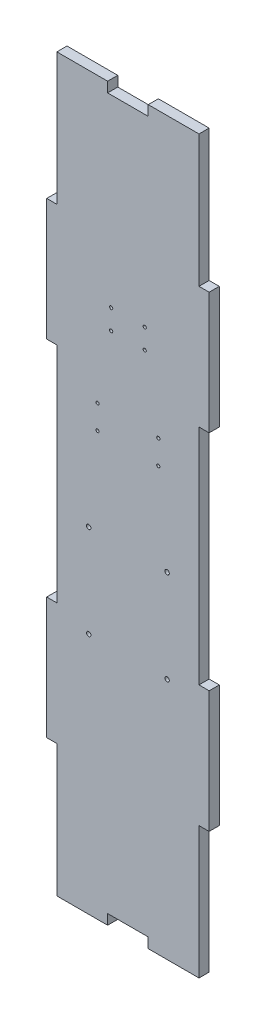
SolidWorks part; units mm, degrees
ref_plane "Front Plane" through (0, 0, 0) normal (0, 0, 1) x (1, 0, 0)
ref_plane "Top Plane" through (0, 0, 0) normal (0, 1, 0) x (1, 0, 0)
ref_plane "Right Plane" through (0, 0, 0) normal (1, 0, 0) x (0, 0, -1)
sketch "Sketch1" plane through (0, 0, 0) normal (0, 0, 1) x (1, 0, 0)
  line L1 (-192.6077, 179.9617) -> (-103.7077, 179.9617)
  line L2 (-192.6077, 179.9617) -> (-192.6077, -277.2383)
  line L3 (-192.6077, -277.2383) -> (-103.7077, -277.2383)
  line L4 (-103.7077, 179.9617) -> (-103.7077, -277.2383)
  dimension "D1" = 457.2
  dimension "D2" = 88.9
extrude "Boss-Extrude1" add sketch "Sketch1" along normal blind 6.35
sketch "Sketch2" plane through (0, 0, 6.35) normal (0, 0, 1) x (1, 0, 0)
  line L0 (-192.6077, 179.9617) -> (-192.6077, -277.2383) construction
  line L1 (-198.9577, 97.4117) -> (-192.6077, 97.4117)
  line L2 (-198.9577, 97.4117) -> (-198.9577, 21.2117)
  line L3 (-198.9577, 21.2117) -> (-192.6077, 21.2117)
  line L4 (-192.6077, 97.4117) -> (-192.6077, 21.2117)
  line L6 (-198.9577, -118.4883) -> (-192.6077, -118.4883)
  line L7 (-198.9577, -118.4883) -> (-198.9577, -194.6883)
  line L8 (-198.9577, -194.6883) -> (-192.6077, -194.6883)
  line L9 (-192.6077, -118.4883) -> (-192.6077, -194.6883)
  line L10 (-148.1577, 179.9617) -> (-148.1577, -277.2383) construction
  line L11 (-103.7077, 179.9617) -> (-192.6077, 179.9617) construction
  line L12 (-192.6077, -277.2383) -> (-103.7077, -277.2383) construction
  line L13 (-97.3577, -194.6883) -> (-103.7077, -194.6883)
  line L14 (-97.3577, -118.4883) -> (-97.3577, -194.6883)
  line L15 (-103.7077, -118.4883) -> (-103.7077, -194.6883)
  line L16 (-97.3577, -118.4883) -> (-103.7077, -118.4883)
  line L17 (-97.3577, 21.2117) -> (-103.7077, 21.2117)
  line L18 (-97.3577, 97.4117) -> (-97.3577, 21.2117)
  line L19 (-103.7077, 97.4117) -> (-103.7077, 21.2117)
  line L20 (-97.3577, 97.4117) -> (-103.7077, 97.4117)
  dimension "D1" = 82.55
  dimension "D4" = 82.55
  dimension "D5" = 6.35
extrude "Boss-Extrude4" add sketch "Sketch2" against normal through all
sketch "Sketch3" plane through (0, 0, 6.35) normal (0, 0, 1) x (1, 0, 0)
  line L0 (-192.6077, -277.2383) -> (-103.7077, -277.2383) construction
  line L1 (-160.8577, -277.2383) -> (-135.4577, -277.2383)
  line L2 (-160.8577, -277.2383) -> (-160.8577, -270.8883)
  line L3 (-160.8577, -270.8883) -> (-135.4577, -270.8883)
  line L4 (-135.4577, -277.2383) -> (-135.4577, -270.8883)
  line L5 (-148.1577, 179.9617) -> (-148.1577, -277.2383) construction
  line L6 (-103.7077, 179.9617) -> (-192.6077, 179.9617) construction
  line L7 (-192.6077, -194.6883) -> (-192.6077, -277.2383) construction
  line L11 (-103.7077, 97.4117) -> (-103.7077, 179.9617) construction
  line L12 (-160.8577, 179.9617) -> (-135.4577, 179.9617)
  line L13 (-160.8577, 179.9617) -> (-160.8577, 173.6117)
  line L14 (-160.8577, 173.6117) -> (-135.4577, 173.6117)
  line L15 (-135.4577, 179.9617) -> (-135.4577, 173.6117)
  dimension "D5" = 6.35
  dimension "D2" = 25.4
  dimension "D3" = 6.35
  dimension "D4" = 25.4
  dimension "D6" = 31.75
  dimension "D1" = 31.75
extrude "Cut-Extrude1" cut sketch "Sketch3" against normal blind 6.35
sketch "Sketch4" plane through (0, 0, 0) normal (0, 0, 1) x (1, 0, 0)
  line L0 (-192.6077, -277.2383) -> (-160.8577, -277.2383) construction
  line L1 (-175.6577, -65.2383) -> (-120.6577, -65.2383) construction
  line L2 (-175.6577, -65.2383) -> (-175.6577, -150.2383) construction
  line L3 (-175.6577, -150.2383) -> (-120.6577, -150.2383) construction
  line L4 (-120.6577, -65.2383) -> (-120.6577, -150.2383) construction
  line L5 (-148.1577, -65.2383) -> (-148.1577, -150.2383) construction
  line L6 (-175.6577, -107.7383) -> (-120.6577, -107.7383) construction
  line L7 (-103.7077, -118.4883) -> (-103.7077, 21.2117) construction
  line L8 (-160.6355, 60.3617) -> (-135.6355, 60.3617) construction
  line L9 (-160.6355, 60.3617) -> (-160.6355, 36.3617) construction
  line L10 (-160.6355, 36.3617) -> (-135.6355, 36.3617) construction
  line L11 (-135.6355, 60.3617) -> (-135.6355, 36.3617) construction
  line L12 (-148.1577, 173.6117) -> (-148.1577, -270.8883) construction
  line L13 (-160.8577, 173.6117) -> (-135.4577, 173.6117) construction
  line L14 (-135.4577, -270.8883) -> (-160.8577, -270.8883) construction
  line L15 (-148.1577, 4.9389) -> (-148.1577, -15.0611) construction
  line L16 (-169.6577, 4.9389) -> (-126.6577, 4.9389) construction
  line L17 (-169.6577, 4.9389) -> (-169.6577, -15.0611) construction
  line L18 (-169.6577, -15.0611) -> (-126.6577, -15.0611) construction
  line L19 (-126.6577, 4.9389) -> (-126.6577, -15.0611) construction
  line L20 (-169.6577, -5.0611) -> (-126.6577, -5.0611) construction
  circle A0 centre (-172.6577, -67.3936) radius 1.375
  circle A1 centre (-123.6577, -67.3936) radius 1.375
  circle A2 centre (-123.6576, -125.3936) radius 1.375
  circle A3 centre (-172.6577, -125.3936) radius 1.375
  circle A4 centre (-158.6355, 58.3617) radius 1
  circle A5 centre (-158.6355, 45.8617) radius 1
  circle A6 centre (-137.6355, 58.3617) radius 1
  circle A7 centre (-137.6355, 45.8617) radius 1
  circle A8 centre (-167.1577, 2.4389) radius 1
  circle A9 centre (-129.1577, 2.4389) radius 1
  circle A10 centre (-129.1577, -12.5611) radius 1
  circle A11 centre (-167.1577, -12.5611) radius 1
  dimension "D5" = 2.75
  dimension "D4" = 2.75
  dimension "D9" = 2
  dimension "D23" = 2
  dimension "D1" = 127
  dimension "D2" = 85
  dimension "D3" = 55
  dimension "D6" = 58
  dimension "D7" = 25
  dimension "D8" = 24
  dimension "D10" = 21
  dimension "D11" = 12.5
  dimension "D12" = 9.5
  dimension "D13" = 2
  dimension "D14" = 2
  dimension "D15" = 2
  dimension "D16" = 31.9278
  dimension "D17" = 101.6
  dimension "D18" = 0
  dimension "D19" = 49
  dimension "D20" = 20
  dimension "D21" = 43
  dimension "D22" = 0
  dimension "D24" = 2.5
  dimension "D25" = 2.5
extrude "Cut-Extrude5" cut sketch "Sketch4" against normal through all and the other way through all
equation "\"width\"= 3.5in"
equation "\"Height\"= 18in"
equation "\"thick\"= 0.25"
equation "\"D1@Sketch1\"=\"Height\""
equation "\"D2@Sketch1\"=\"width\""
equation "\"D1@Boss-Extrude1\"=\"thick\""
equation "\"D5@Sketch2\"=\"thick\""
equation "\"D1\"= \"thick\""
equation "\"D3@Sketch3\"=\"thick\""
equation "\"D1@Cut-Extrude1\"=\"thick\""
equation "\"D5@Sketch3\"=\"thick\""
equation "\"D2@Cut-Extrude5\"=\"thick\""
